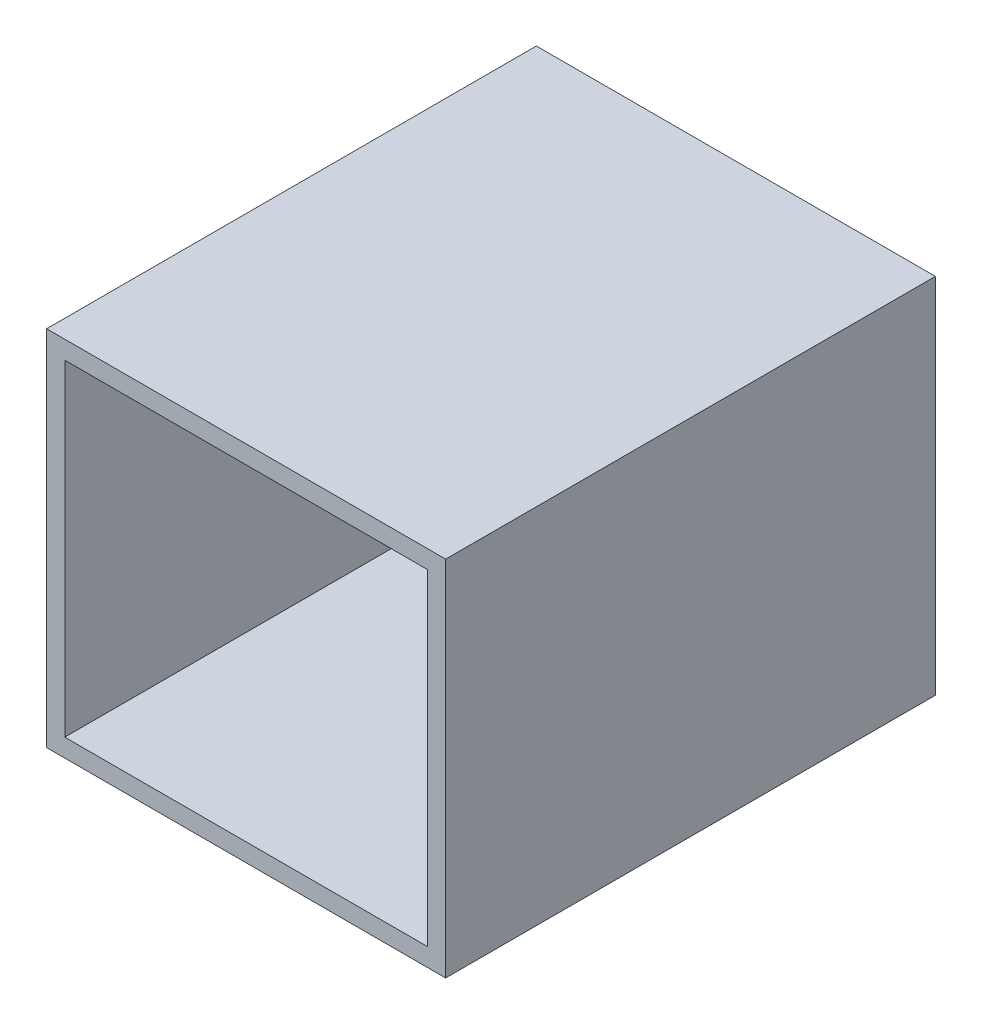
SolidWorks part; units mm, degrees
ref_plane "Front Plane" through (0, 0, 0) normal (0, 0, 1) x (1, 0, 0)
ref_plane "Top Plane" through (0, 0, 0) normal (0, 1, 0) x (1, 0, 0)
ref_plane "Right Plane" through (0, 0, 0) normal (1, 0, 0) x (0, 0, -1)
sketch "Sketch2" plane through (0, 0, 0) normal (0, 0, 1) x (1, 0, 0)
  line L1 (-11, -10) -> (11, -10)
  line L2 (-11, -10) -> (-11, 10)
  line L3 (-11, 10) -> (11, 10)
  line L4 (11, -10) -> (11, 10)
  line L5 (-11, -10) -> (11, 10) construction
  line L6 (-11, 10) -> (11, -10) construction
  line L7 (-10, -9) -> (10, -9)
  line L8 (-10, -9) -> (-10, 9)
  line L9 (-10, 9) -> (10, 9)
  line L10 (10, -9) -> (10, 9)
  line L11 (-10, -9) -> (10, 9) construction
  line L12 (-10, 9) -> (10, -9) construction
  point P0 (0, 0)
  point P6 (0, 0)
  point P11 (6, -4)
  point P12 (6, -4)
  dimension "D1" = 20
  dimension "D2" = 22
  dimension "D3" = 18
  dimension "D4" = 20
extrude "Boss-Extrude1" add sketch "Sketch2" along normal blind 10
extrude "Boss-Extrude2" add sketch "Sketch2<2>" against normal blind 1 contours L7 L10 L9 L8 region at (0, 0, 0)
sketch "Sketch2<2>" plane through (0, 0, 0) normal (0, 0, 1) x (1, 0, 0) same geometry as "Sketch2"
extrude "Boss-Extrude3" add sketch "Sketch2<3>" against normal blind 1 contours L1 L4 L3 L2 L10 L7 L8 L9 region at (-10.7027, 0, 0)
sketch "Sketch2<3>" plane through (0, 0, 0) normal (0, 0, 1) x (1, 0, 0) same geometry as "Sketch2"
extrude "Boss-Extrude4" add sketch "Sketch2<4>" along normal blind 26
sketch "Sketch2<4>" plane through (0, 0, 0) normal (0, 0, 1) x (1, 0, 0) same geometry as "Sketch2"
